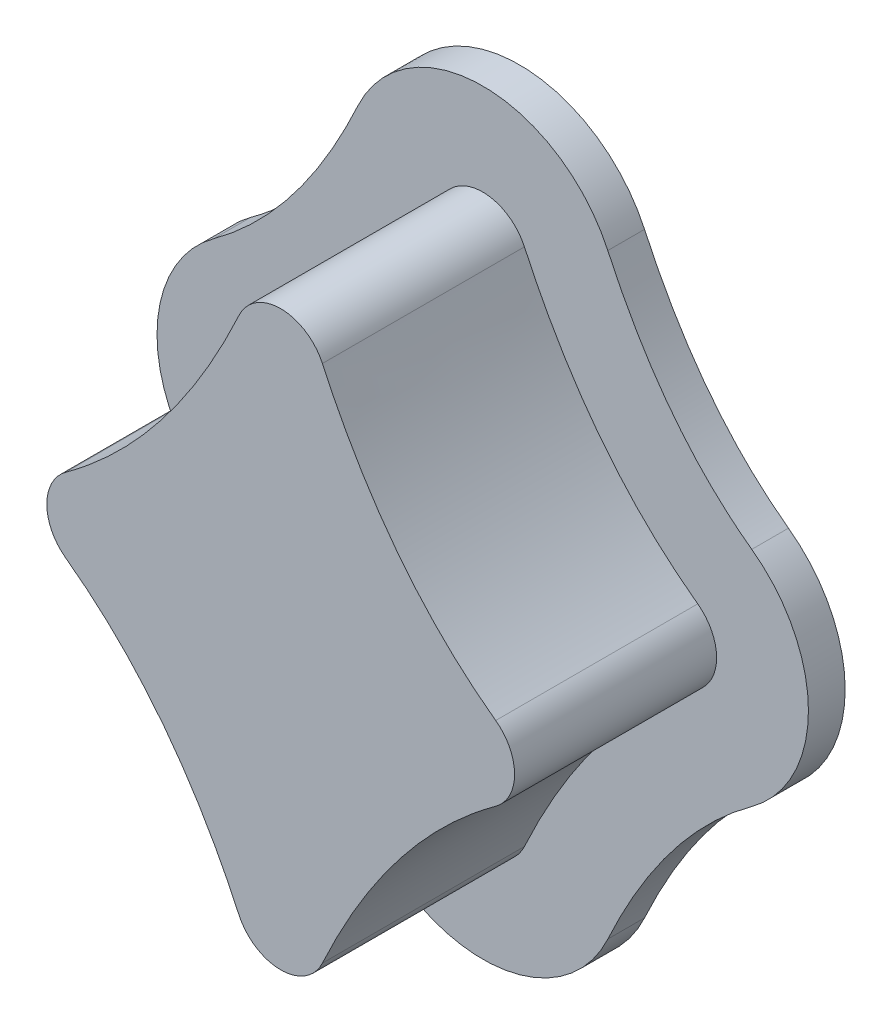
SolidWorks part; units mm, degrees
ref_plane "Front Plane" through (0, 0, 0) normal (0, 0, 1) x (1, 0, 0)
ref_plane "Top Plane" through (0, 0, 0) normal (0, 1, 0) x (1, 0, 0)
ref_plane "Right Plane" through (0, 0, 0) normal (1, 0, 0) x (0, 0, -1)
sketch "Sketch4" plane through (0, 0, 0) normal (0, 0, 1) x (1, 0, 0)
  line L0 (0, 4) -> (0, 0) construction
  line L1 (0, 0) -> (3, 0) construction
  line L6 (0, 4) -> (-0.4714, 5.4509) construction
  line L7 (3, 0) -> (4.5481, -0.7888) construction
  spline S0 degree 3 poles (0, 4) (0.515, 2.4149) (1.3631, 0.834) (3, 0) knots 0 0 0 0 1 1 1 1
  spline S1 degree 3 poles (0, 4) (-0.515, 2.4149) (-1.3631, 0.834) (-3, 0) knots 0 0 0 0 1 1 1 1
  spline S2 degree 3 poles (0, -4) (0.515, -2.4149) (1.3631, -0.834) (3, 0) knots 0 0 0 0 1 1 1 1
  spline S3 degree 3 poles (0, -4) (-0.515, -2.4149) (-1.3631, -0.834) (-3, 0) knots 0 0 0 0 1 1 1 1
  dimension "D1" = 4
  dimension "D2" = 3
  dimension "D3" = 27
  dimension "D4" = 18
extrude "Boss-Extrude1" add sketch "Sketch4" along normal blind 2.6
fillet "Fillet1" radius 0.5 4 edges at (0, -4, 1.3) (-3, 0, 1.3) (3, 0, 1.3) (0, 4, 1.3)
ref_axis "Axis1" through (0, 0, -0.1) along (0, 0, 1)
sketch "Sketch5" plane through (0, 0, 0) normal (0, 0, 1) x (1, 0, 0)
  arc A44 (-2.9297, 1.2126) -> (-2.9297, -1.2126) centre (-2.0467, 0) ccw
  arc A45 (-1.362, -3.2466) -> (1.362, -3.2466) centre (0, -2.6181) ccw
  arc A46 (2.9297, -1.2126) -> (2.9297, 1.2126) centre (2.0467, 0) ccw
  arc A47 (1.362, 3.2466) -> (-1.362, 3.2466) centre (0, 2.6181) ccw
  arc A48 (-2.9297, 1.2126) -> (-2.9297, -1.2126) centre (-2.0467, 0) ccw
  arc A49 (-1.362, -3.2466) -> (1.362, -3.2466) centre (0, -2.6181) ccw
  arc A50 (2.9297, -1.2126) -> (2.9297, 1.2126) centre (2.0467, 0) ccw
  arc A51 (1.362, 3.2466) -> (-1.362, 3.2466) centre (0, 2.6181) ccw
  spline S20 degree 3 poles (1613.3912, -2524.9289) (-106.3856, 136.2609) (12.0922, 21.0369) (-14.657, -14.8148) (-135.879, 48.7811) (-542.284, 2949.6818) knots -26.781298 -26.781298 -26.781298 -26.781298 0.5 0.5 24.943347 24.943347 24.943347 24.943347 only from (-1.362, 3.2466) to (-2.9297, 1.2126)
  spline S21 degree 3 poles (-2088.2019, -2157.2388) (-166.6922, -110.4258) (-18.9675, 15.0255) (-2.287, -1.7881) (-2.1458, -1.9539) (12.0658, -20.9981) (-105.7475, -136.1634) (1583.4199, 2543.778) knots -26.927123 -26.927123 -26.927123 -26.927123 0.25 0.25 0.5 0.5 27.721075 27.721075 27.721075 27.721075 only from (-2.9297, -1.2126) to (-1.362, -3.2466)
  spline S22 degree 3 poles (-1613.3912, 2524.9289) (106.3856, -136.2609) (-12.0922, -21.0369) (14.657, 14.8148) (135.879, -48.7811) (542.284, -2949.6818) knots -26.781298 -26.781298 -26.781298 -26.781298 0.5 0.5 24.943347 24.943347 24.943347 24.943347 only from (1.362, -3.2466) to (2.9297, -1.2126)
  spline S23 degree 3 poles (2088.2019, 2157.2388) (166.6922, 110.4258) (18.9675, -15.0255) (2.287, 1.7881) (2.1458, 1.9539) (-12.0658, 20.9981) (105.7475, 136.1634) (-1583.4199, -2543.778) knots -26.927123 -26.927123 -26.927123 -26.927123 0.25 0.25 0.5 0.5 27.721075 27.721075 27.721075 27.721075 only from (2.9297, 1.2126) to (1.362, 3.2466)
  spline S24 degree 3 poles (-1.362, 3.2466) (-1.5436, 2.853) (-1.7576, 2.4741) (-2.2748, 1.781) (-2.5788, 1.4681) (-2.9297, 1.2126) knots 0 0 0 0 0.5 0.5 1 1 1 1
  spline S25 degree 3 poles (-2.9297, -1.2126) (-2.7542, -1.3404) (-2.5911, -1.4816) (-2.287, -1.7881) (-2.1458, -1.9539) (-1.7578, -2.4738) (-1.5436, -2.8529) (-1.362, -3.2466) knots 0 0 0 0 0.25 0.25 0.5 0.5 1 1 1 1
  spline S26 degree 3 poles (1.362, -3.2466) (1.5436, -2.853) (1.7576, -2.4741) (2.2748, -1.781) (2.5788, -1.4681) (2.9297, -1.2126) knots 0 0 0 0 0.5 0.5 1 1 1 1
  spline S27 degree 3 poles (2.9297, 1.2126) (2.7542, 1.3404) (2.5911, 1.4816) (2.287, 1.7881) (2.1458, 1.9539) (1.7578, 2.4738) (1.5436, 2.8529) (1.362, 3.2466) knots 0 0 0 0 0.25 0.25 0.5 0.5 1 1 1 1
  dimension "D1" = 1
extrude "Boss-Extrude2" add sketch "Sketch5" along normal blind 0.4
